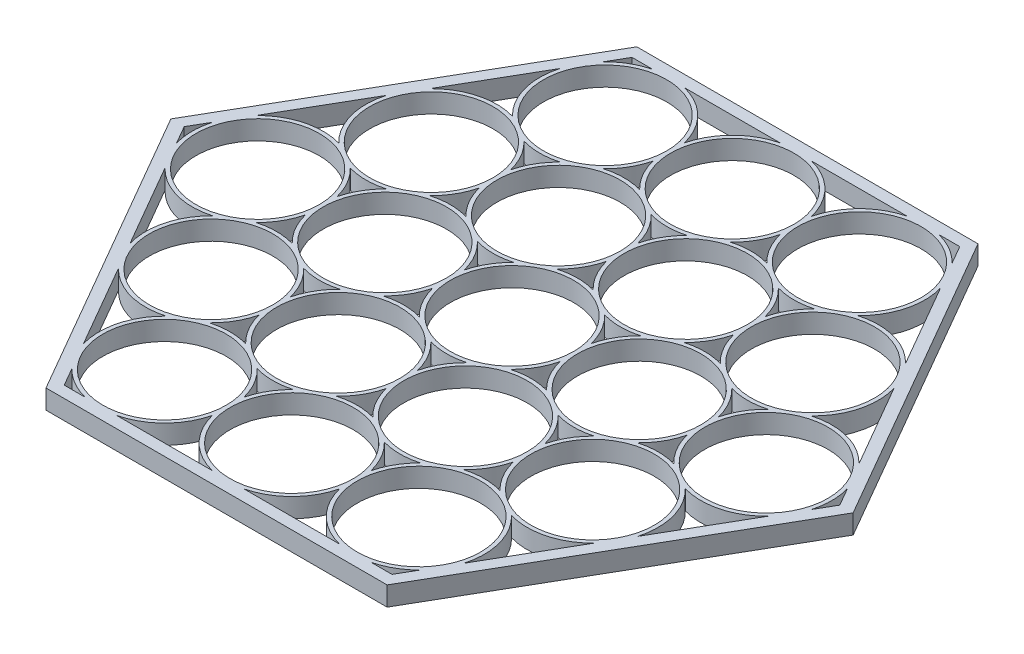
SolidWorks part; units mm, degrees
ref_plane "Front Plane" through (0, 0, 0) normal (0, 0, 1) x (1, 0, 0)
ref_plane "Top Plane" through (0, 0, 0) normal (0, 1, 0) x (1, 0, 0)
ref_plane "Right Plane" through (0, 0, 0) normal (1, 0, 0) x (0, 0, -1)
sketch "Sketch1" plane through (0, 0, 0) normal (0, 1, 0) x (1, 0, 0)
  line L1 (-16.5, -28.5788) -> (16.5, -28.5788) construction
  line L2 (16.5, -28.5788) -> (33, 0) construction
  line L3 (33, 0) -> (16.5, 28.5788) construction
  line L4 (16.5, 28.5788) -> (-16.5, 28.5788) construction
  line L5 (-16.5, 28.5788) -> (-33, 0) construction
  line L6 (-33, 0) -> (-16.5, -28.5788) construction
  line L7 (-33, -57.1577) -> (33, -57.1577) construction
  line L8 (33, -57.1577) -> (66, 0) construction
  line L9 (66, 0) -> (33, 57.1577) construction
  line L10 (33, 57.1577) -> (-33, 57.1577) construction
  line L11 (-33, 57.1577) -> (-66, 0) construction
  line L12 (-66, 0) -> (-33, -57.1577) construction
  line L13 (-42.5263, -73.6577) -> (42.5263, -73.6577)
  line L14 (42.5263, -73.6577) -> (85.0526, 0)
  line L15 (85.0526, 0) -> (42.5263, 73.6577)
  line L16 (42.5263, 73.6577) -> (-42.5263, 73.6577)
  line L17 (-42.5263, 73.6577) -> (-85.0526, 0)
  line L18 (-85.0526, 0) -> (-42.5263, -73.6577)
  circle A0 centre (0, 0) radius 33 construction
  circle A1 centre (0, 0) radius 16.5
  circle A2 centre (-16.5, 28.5788) radius 16.5
  circle A3 centre (16.5, 28.5788) radius 16.5
  circle A4 centre (33, 0) radius 16.5
  circle A5 centre (16.5, -28.5788) radius 16.5
  circle A6 centre (-16.5, -28.5788) radius 16.5
  circle A7 centre (-33, 0) radius 16.5
  circle A8 centre (0, 0) radius 57.1577 construction
  circle A9 centre (-49.5, 28.5788) radius 16.5
  circle A10 centre (0, 57.1577) radius 16.5
  circle A11 centre (49.5, 28.5788) radius 16.5
  circle A12 centre (49.5, -28.5788) radius 16.5
  circle A13 centre (0, -57.1577) radius 16.5
  circle A14 centre (-49.5, -28.5788) radius 16.5
  circle A15 centre (-66, 0) radius 16.5
  circle A16 centre (-33, 57.1577) radius 16.5
  circle A17 centre (33, 57.1577) radius 16.5
  circle A18 centre (66, 0) radius 16.5
  circle A19 centre (33, -57.1577) radius 16.5
  circle A20 centre (-33, -57.1577) radius 16.5
  circle A21 centre (0, 0) radius 73.6577 construction
  point P24 (0, 0)
  point P44 (0, 0)
  point P56 (0, 0)
  dimension "D1" = 66
  dimension "D2" = 33
  dimension "D4" = 33
  dimension "D5" = 6
  dimension "D3" = 6
  dimension "D6" = 6
extrude "Extrude-Thin1" add sketch "Sketch1" along normal blind 5 thin contours A20 | A13 | A19 | A12 | A18 | A11 | A4 | A5 | A6 | A14 | A15 | A1 | A3 | A7 | A2 | A9 | A16 | A10 | A17 thin type mid plane wall 1
extrude "Extrude-Thin2" add sketch "Sketch1<3>" along normal blind 5 thin contours L15 L16 L17 L18 L13 L14 thin type one direction wall 3
sketch "Sketch1<3>" plane through (0, 0, 0) normal (0, 1, 0) x (1, 0, 0) same geometry as "Sketch1"
